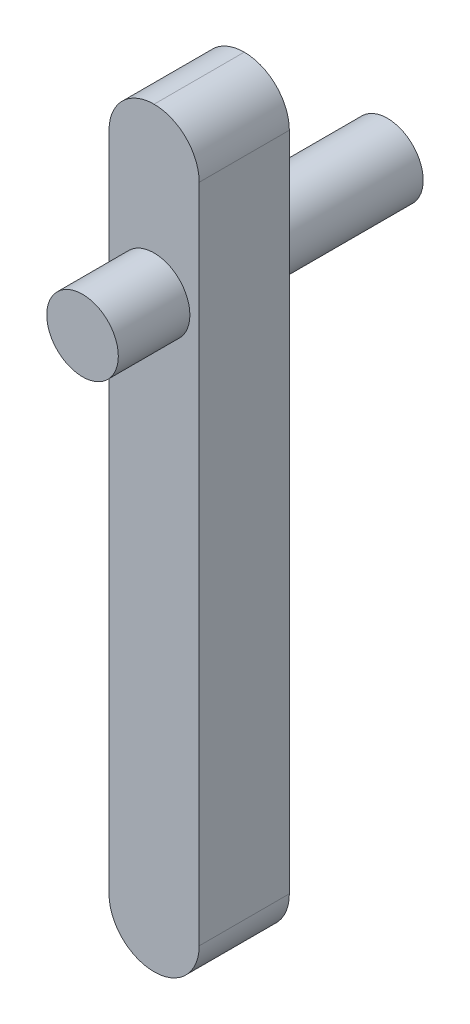
SolidWorks part; units mm, degrees
ref_plane "Front Plane" through (0, 0, 0) normal (0, 0, 1) x (1, 0, 0)
ref_plane "Top Plane" through (0, 0, 0) normal (0, 1, 0) x (1, 0, 0)
ref_plane "Right Plane" through (0, 0, 0) normal (1, 0, 0) x (0, 0, -1)
sketch "Sketch1" plane through (0, 0, 0) normal (0, 0, 1) x (1, 0, 0)
  line L0 (4, 31.75) -> (4, 34.925)
  line L2 (-4, 31.75) -> (-4, -31.75)
  line L3 (-4, -31.75) -> (4, -31.75)
  line L4 (4, 31.75) -> (4, -31.75)
  line L5 (-4, 31.75) -> (4, -31.75) construction
  line L6 (-4, -31.75) -> (4, 31.75) construction
  line L7 (4, 34.925) -> (-4, 34.925)
  line L8 (-4, 34.925) -> (-4, 31.75)
  line L9 (-4, 31.75) -> (4, 31.75) construction
  point P0 (0, 0)
  dimension "D1" = 8
  dimension "D2" = 63.5
  dimension "D3" = 34.925
extrude "Boss-Extrude1" add sketch "Sketch1" along normal blind 8
fillet "Fillet1" radius 4 4 edges at (-4, -31.75, 4) (4, -31.75, 4) (4, 34.925, 4) (-4, 34.925, 4)
sketch "Sketch2" plane through (0, 0, 8) normal (0, 0, 1) x (1, 0, 0)
  circle A0 centre (0, 20.32) radius 3.175
  dimension "D1" = 6.35
  dimension "D2" = 20.32
extrude "Boss-Extrude2" add sketch "Sketch2" along normal blind 6.35 and the other way blind 20.7
